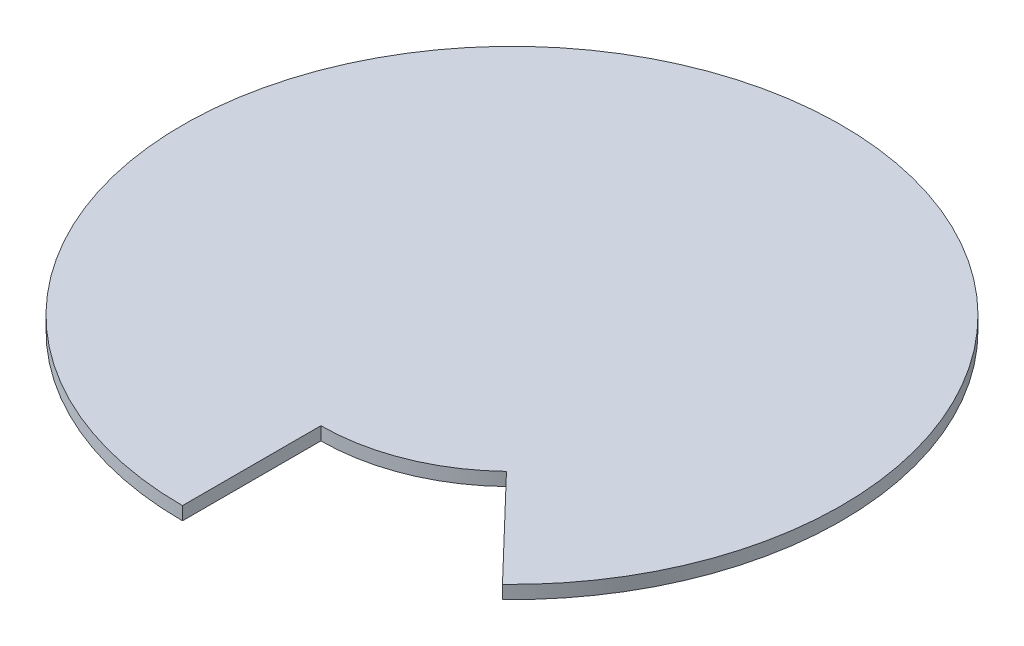
SolidWorks part; units mm, degrees
ref_plane "Front Plane" through (0, 0, 0) normal (0, 0, 1) x (1, 0, 0)
ref_plane "Top Plane" through (0, 0, 0) normal (0, 1, 0) x (1, 0, 0)
ref_plane "Right Plane" through (0, 0, 0) normal (1, 0, 0) x (0, 0, -1)
sketch "Sketch1" plane through (0, 0, 0) normal (0, 1, 0) x (1, 0, 0)
  circle A0 centre (0, 0) radius 100
  dimension "D1" = 200
extrude "Boss-Extrude1" add sketch "Sketch1" along normal blind 4
sketch "Sketch3" plane through (0, 4, 0) normal (0, 1, 0) x (1, 0, 0)
  line L0 (0, -100) -> (0, -58)
  line L2 (40.1662, -41.8411) -> (69.2521, -72.1398)
  line L4 (0, 0) -> (0, -100) construction
  arc A0 (0, -100) -> (69.2521, -72.1398) centre (0, 0) ccw
  circle A1 centre (0, 0) radius 100 construction
  arc A2 (0, -58) -> (40.1662, -41.8411) centre (0, 0) ccw
  point P7 (0, -58.0035)
  point P9 (0, -58)
  point P10 (0, 0)
  point P11 (-0.317, -99.9995)
  dimension "D4" = 58
  dimension "D3" = 43.83
extrude "Cut-Extrude1" cut sketch "Sketch3" against normal blind 10
